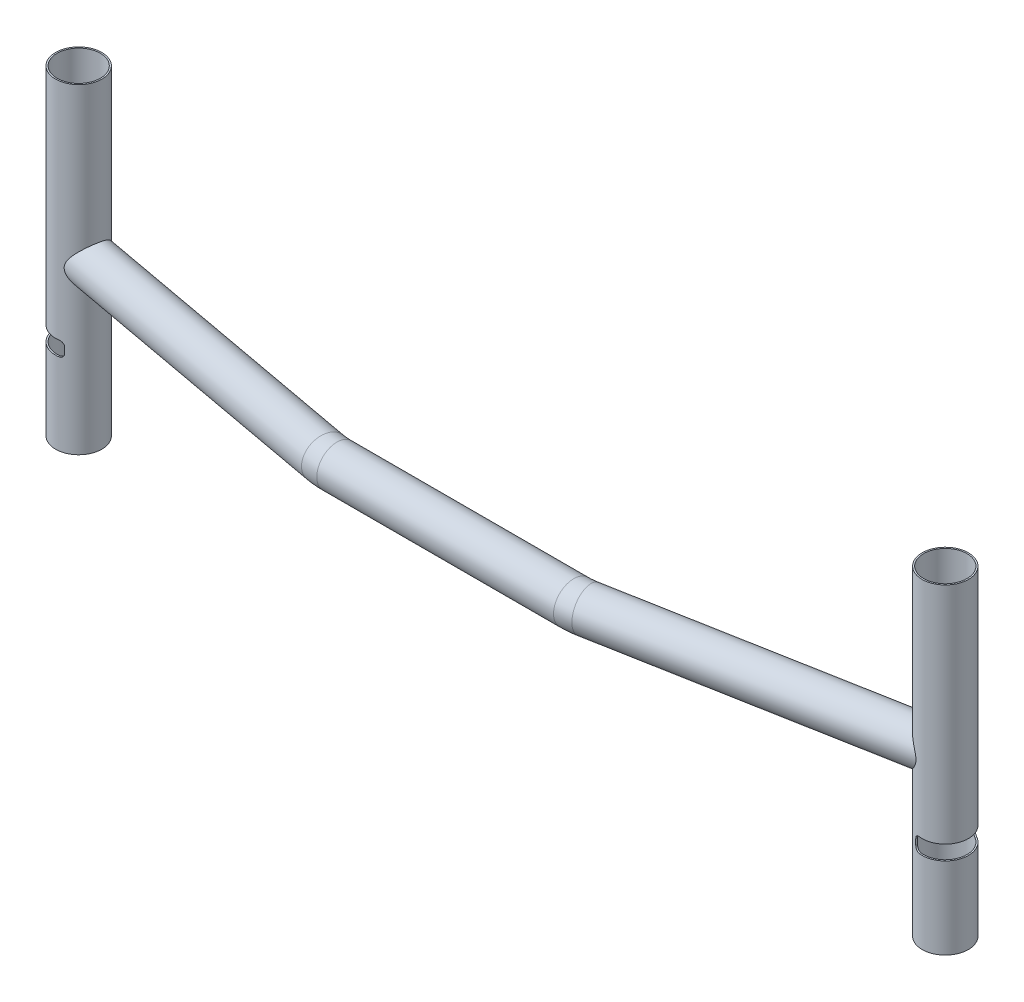
SolidWorks part; units mm, degrees
ref_plane "Front Plane" through (0, 0, 0) normal (0, 0, 1) x (1, 0, 0)
ref_plane "Top Plane" through (0, 0, 0) normal (0, 1, 0) x (1, 0, 0)
ref_plane "Right Plane" through (0, 0, 0) normal (1, 0, 0) x (0, 0, -1)
sketch "Sketch1" plane through (0, 0, 0) normal (0, 1, 0) x (1, 0, 0)
  line L0 (0, 0) -> (0, 107.988) construction
  line L1 (-65, 0) -> (65, 0)
  line L2 (72.225, 0.6579) -> (232, 30)
  line L3 (-72.225, 0.6579) -> (-232, 30)
  arc A0 (72.225, 0.6579) -> (65, 0) centre (65, 40) cw
  arc A1 (-72.225, 0.6579) -> (-65, 0) centre (-65, 40) ccw
  dimension "D2" = 40
  dimension "D1" = 232
  dimension "D3" = 65
  dimension "D4" = 30
ref_plane "Plane1" through (232, 0, -30) normal (0.9836, 0, -0.1806) x (-0.1806, 0, -0.9836)
sketch "Sketch2" plane through (232, 0, -30) normal (0.9836, 0, -0.1806) x (-0.1806, 0, -0.9836)
  line L0 (0.6579, 0) -> (0, 0) construction
  circle A0 centre (0, 0) radius 11.1
  circle A1 centre (0, 0) radius 10.3
  dimension "D1" = 0.8
sweep "Sweep1" add profiles "Sketch2" path "Sketch1"
sketch "Sketch3" plane through (0, 0, 0) normal (0, 1, 0) x (1, 0, 0)
  line L0 (229.9951, 40.9174) -> (234.0049, 19.0826) construction
  line L1 (229.9951, 40.9174) -> (232, 30) construction
  line L2 (232, 30) -> (237.9013, 31.0838) construction
  circle A0 centre (237.9013, 31.0838) radius 12.7
  circle A1 centre (237.9013, 31.0838) radius 11.9
  dimension "D1" = 0.8
  dimension "D3" = 25.4
  dimension "D4" = 0.8
  dimension "D2" = 6
extrude "Boss-Extrude1" add sketch "Sketch3" along normal blind 88 and the other way blind 88
sketch "Sketch4" plane through (0, -88, 0) normal (0, -1, 0) x (1, 0, 0)
  circle A0 centre (237.9013, -31.0838) radius 11.9
extrude "Cut-Extrude1" cut sketch "Sketch4" against normal through all
sketch "Sketch5" plane through (232, 0, -30) normal (0.9836, 0, -0.1806) x (-0.1806, 0, -0.9836)
  circle A0 centre (-0.0149, 0) radius 10.7
  dimension "D1" = 21.4
extrude "Cut-Extrude2" cut sketch "Sketch5" against normal blind 88
sketch "Sketch6" plane through (0, 88, 0) normal (0, 1, 0) x (1, 0, 0)
  line L0 (237.9013, 31.0838) -> (72.225, 0.6579)
  line L1 (70.2201, 11.5753) -> (74.23, -10.2595) construction
  line L2 (237.9013, 31.0838) -> (241.892, 42.2947)
  circle A0 centre (237.9013, 31.0838) radius 11.9 construction
  dimension "D1" = 60
ref_plane "Plane2" through (237.9013, 88, -31.0838) normal (0.3353, 0, -0.9421) x (-0.9421, 0, -0.3353)
sketch "Sketch7" plane through (237.9013, 88, -31.0838) normal (0.3353, 0, -0.9421) x (-0.9421, 0, -0.3353)
  line L0 (0, -176) -> (0, -127.2306) construction
  line L1 (-12.7, -176) -> (12.7, -176) construction
  line L4 (-2.5, -123.2306) -> (-12.7, -123.2306)
  line L5 (-2.5, -131.2306) -> (-12.7, -131.2306)
  line L6 (-12.7, -123.2306) -> (-12.7, -131.2306)
  line L7 (0, -125.7306) -> (0, -128.7306)
  arc A0 (0, -125.7306) -> (-2.5, -123.2306) centre (-2.5, -125.7306) ccw
  arc A1 (0, -128.7306) -> (-2.5, -131.2306) centre (-2.5, -128.7306) cw
  dimension "D1" = 2.5
extrude "Cut-Extrude3" cut sketch "Sketch7" against normal blind 20 and the other way blind 20
mirror "Mirror1" about plane through (0, 0, 0) normal (1, 0, 0) of "Cut-Extrude1", "Boss-Extrude1", "Cut-Extrude3", "Cut-Extrude2"
sketch "Sketch8" plane through (0, 0, 0) normal (0, 1, 0) x (1, 0, 0)
  line L0 (72.225, 0.6579) -> (216.9875, 26.5937) construction
  line L1 (70.2201, 11.5753) -> (74.23, -10.2595) construction
  circle A0 centre (216.9875, 26.5937) radius 3
extrude "Cut-Extrude4" cut sketch "Sketch8" against normal up to next
ref_plane "Plane3" through (0, 0, -50) normal (0, 0, 1) x (1, 0, 0)
sketch "Sketch11" plane through (0, 0, -50) normal (0, 0, 1) x (1, 0, 0)
  line L0 (225.2013, -88) -> (250.6013, -88) construction
  line L1 (235.9013, -94) -> (239.9013, -94)
  line L2 (235.9013, -94) -> (235.9013, -82)
  line L3 (235.9013, -82) -> (239.9013, -82)
  line L4 (239.9013, -94) -> (239.9013, -82)
  line L5 (235.9013, -94) -> (239.9013, -82) construction
  line L6 (235.9013, -82) -> (239.9013, -94) construction
  point P0 (237.9013, -88)
  dimension "D1" = 12
  dimension "D2" = 4
extrude "Cut-Extrude6" cut sketch "Sketch11" along normal up to next
mirror "Mirror2" about plane through (0, 0, 0) normal (1, 0, 0) of "Cut-Extrude6"
